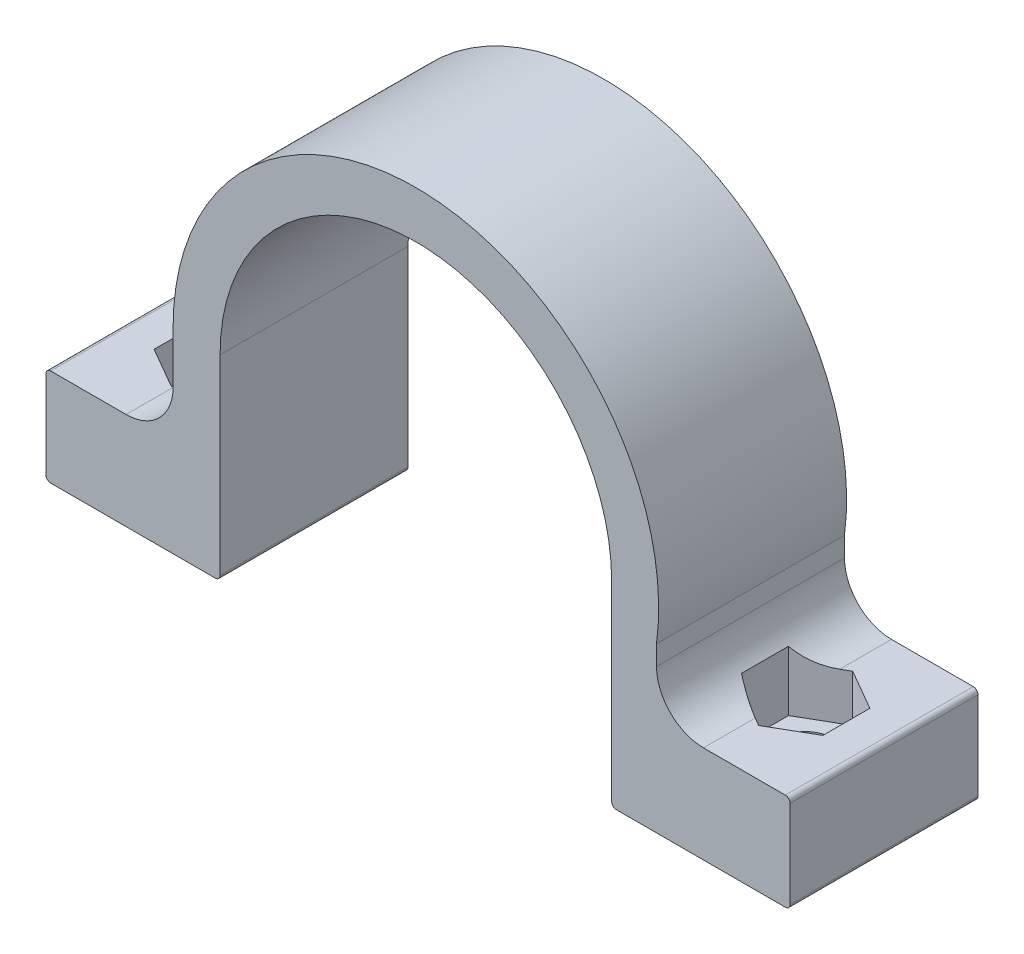
SolidWorks part; units mm, degrees
ref_plane "Front Plane" through (0, 0, 0) normal (0, 0, 1) x (1, 0, 0)
ref_plane "Top Plane" through (0, 0, 0) normal (0, 1, 0) x (1, 0, 0)
ref_plane "Right Plane" through (0, 0, 0) normal (1, 0, 0) x (0, 0, -1)
sketch "Sketch1" plane through (0, 0, 0) normal (0, 0, 1) x (1, 0, 0)
  line L0 (-12.5, 0) -> (-12.5, -12.5)
  line L1 (-23.6129, -6.3) -> (-15.5, -6.3)
  line L2 (-23.6129, -6.3) -> (-23.6129, -12.5)
  line L3 (-23.6129, -12.5) -> (23.8884, -12.5)
  line L4 (23.8884, -6.3) -> (23.8884, -12.5)
  line L5 (12.5, 0) -> (12.5, -12.5)
  line L6 (-15.5, 0) -> (-15.5, -6.3)
  line L8 (23.8884, -6.3) -> (15.364, -6.3)
  line L9 (15.364, -6.3) -> (15.364, -2.0488)
  arc A0 (12.5, 0) -> (-12.5, 0) centre (0, 0) ccw
  arc A1 (15.364, -2.0488) -> (-15.5, 0) centre (0, 0) ccw
  dimension "D1" = 25
  dimension "D2" = 31
  dimension "D4" = 6.2
  dimension "D6" = 12.5
  dimension "D7" = 6.2
extrude "Boss-Extrude1" add sketch "Sketch1" along normal blind 12 contours A1 L1 L2 L3 L0 A0 L5 L4 region at (-13.0514, -6.25, 0)
sketch "Sketch2" plane through (0, -6.3, 0) normal (0, 1, 0) x (1, 0, 0)
  line L0 (0, 0) -> (0, -16.3354) construction
  line L2 (-23.6129, -12) -> (-23.6129, 0) construction
  line L3 (23.8884, -12) -> (23.8884, 0) construction
  circle A2 centre (-18.6129, -6) radius 1.65
  circle A3 centre (18.8884, -6) radius 1.65
  dimension "D1" = 3.3
  dimension "D3" = 3.3
  dimension "D2" = 5
  dimension "D4" = 5
extrude "Cut-Extrude1" cut sketch "Sketch2" against normal through all
sketch "Sketch3" plane through (0, -6.3, 0) normal (0, 1, 0) x (1, 0, 0)
  line L0 (-15.5, -12) -> (-15.5, 0) construction
  line L1 (18.8884, -3) -> (16.2903, -4.5)
  line L2 (16.2903, -4.5) -> (16.2903, -7.5)
  line L3 (16.2903, -7.5) -> (18.8884, -9)
  line L4 (18.8884, -9) -> (21.4865, -7.5)
  line L5 (21.4865, -7.5) -> (21.4865, -4.5)
  line L6 (21.4865, -4.5) -> (18.8884, -3)
  line L7 (-18.6129, -9) -> (-16.0148, -7.5)
  line L8 (-16.0148, -7.5) -> (-16.0148, -4.5)
  line L9 (-16.0148, -4.5) -> (-18.6129, -3)
  line L10 (-18.6129, -3) -> (-21.2109, -4.5)
  line L11 (-21.2109, -4.5) -> (-21.2109, -7.5)
  line L12 (-21.2109, -7.5) -> (-18.6129, -9)
  line L13 (15.364, -12) -> (15.364, 0) construction
  circle A0 centre (18.8884, -6) radius 2.5981 construction
  circle A1 centre (-18.6129, -6) radius 2.5981 construction
  dimension "D1" = 3
  dimension "D2" = 3
extrude "Cut-Extrude2" cut sketch "Sketch3" against normal blind 3
fillet "Fillet2" radius 3 2 edges at (-15.5, -6.3, 6) (15.364, -6.3, 6)
fillet "Fillet3" radius 0.3 6 edges at (23.8884, -12.5, 6) (23.8884, -6.3, 6) (12.5, -12.5, 6) (-12.5, -12.5, 6) (-23.6129, -12.5, 6) (-23.6129, -6.3, 6)
